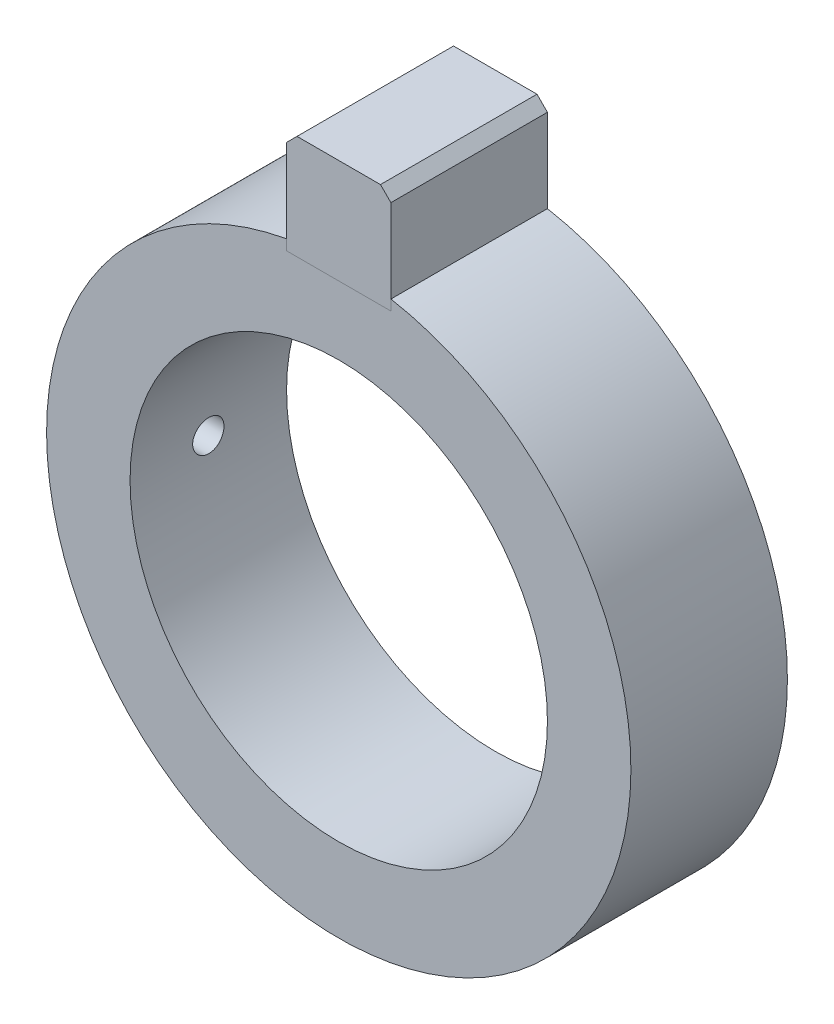
SolidWorks part; units mm, degrees
note: '?' marks a value the reader was unsure of.
ref_plane "Front Plane" through (0, 0, 0) normal (0, 0, 1) x (1, 0, 0)
ref_plane "Top Plane" through (0, 0, 0) normal (0, 1, 0) x (1, 0, 0)
ref_plane "Right Plane" through (0, 0, 0) normal (1, 0, 0) x (0, 0, -1)
sketch "Sketch1" plane through (0, 0, 0) normal (0, 0, 1) x (1, 0, 0)
  circle A0 centre (0, 0) radius 20
  circle A1 centre (0, 0) radius 28
  dimension "D1" = 56
  dimension "D2" = 40
extrude "Boss-Extrude1" add sketch "Sketch1" along normal blind 15
ref_axis "Axis1" through (0, 0, 0) along (-1, 0, 0)?
ref_plane "Plane1" through (-28, 0, 0) normal (-1, 0, 0) x (0, 0, 1)
sketch "Sketch2" plane through (-28, 0, 0) normal (-1, 0, 0) x (0, 0, 1)
  line L0 (0, 0) -> (15, 0) construction
  circle A0 centre (7.5, 0) radius 1.5
  dimension "D1" = 15
  dimension "D2" = 3
extrude "Cut-Extrude1" cut sketch "Sketch2" against normal up to surface (8 mm away) up to face at (20, 0, 15)
sketch "Sketch3" plane through (0, 0, 0) normal (0, 0, -1) x (-1, 0, 0)
  line L0 (0, 20) -> (0, 28) construction
  line L1 (-5, 27.55) -> (5, 27.55)
  line L2 (5, 27.55) -> (5, 28)
  line L3 (5, 28) -> (-5, 28)
  line L4 (-5, 28) -> (-5, 27.55)
  line L5 (5, 27.55) -> (5, 26.55)
  line L6 (5, 26.55) -> (-5, 26.55)
  line L7 (-5, 26.55) -> (-5, 27.55)
  circle A0 centre (0, 0) radius 20 construction
  circle A1 centre (0, 0) radius 28 construction
  point P11 (0, 27.55)
  point P14 (0, 28)
  circle M5 centre (0, 0) radius 28
  dimension "D1" = 10
  dimension "D2" = 1
extrude "Cut-Extrude2" cut sketch "Sketch3" against normal up to surface (15 mm away) contours L0 L1 M5 | L1 L0 M5 | L6 L0 L1 L7 | L0 L6 L5 L1 up to face at (28, 0, 15)
sketch "Sketch5" plane through (0, 26.55, 0) normal (0, 1, 0) x (1, 0, 0)
  line L0 (5, -15) -> (5, 0)
  line L1 (5, 0) -> (-5, 0)
  line L2 (-5, 0) -> (-5, -15)
  line L3 (-5, -15) -> (5, -15)
extrude "Boss-Extrude2" add sketch "Sketch5" along normal blind 10 separate body
sketch "Sketch6" plane through (0, 0, 0) normal (0, 0, -1) x (-1, 0, 0)
  line L0 (-5, 36.55) -> (-5, 35.55)
  line L1 (-5, 36.55) -> (-5, 26.55) construction
  line L2 (-5, 36.55) -> (-4, 36.55)
  line L3 (-5, 36.55) -> (5, 36.55) construction
  line L4 (-4, 36.55) -> (-5, 35.55)
  line L5 (0, 26.55) -> (0, 36.55) construction
  line L6 (5, 26.55) -> (-5, 26.55) construction
  line L7 (5, 36.55) -> (4, 36.55)
  line L8 (5, 36.55) -> (5, 35.55)
  line L9 (4, 36.55) -> (5, 35.55)
  dimension "D1" = 1
  dimension "D2" = 1
extrude "Cut-Extrude3" cut sketch "Sketch6" against normal up to surface (15 mm away) up to face at (0, 31.55, 15)
